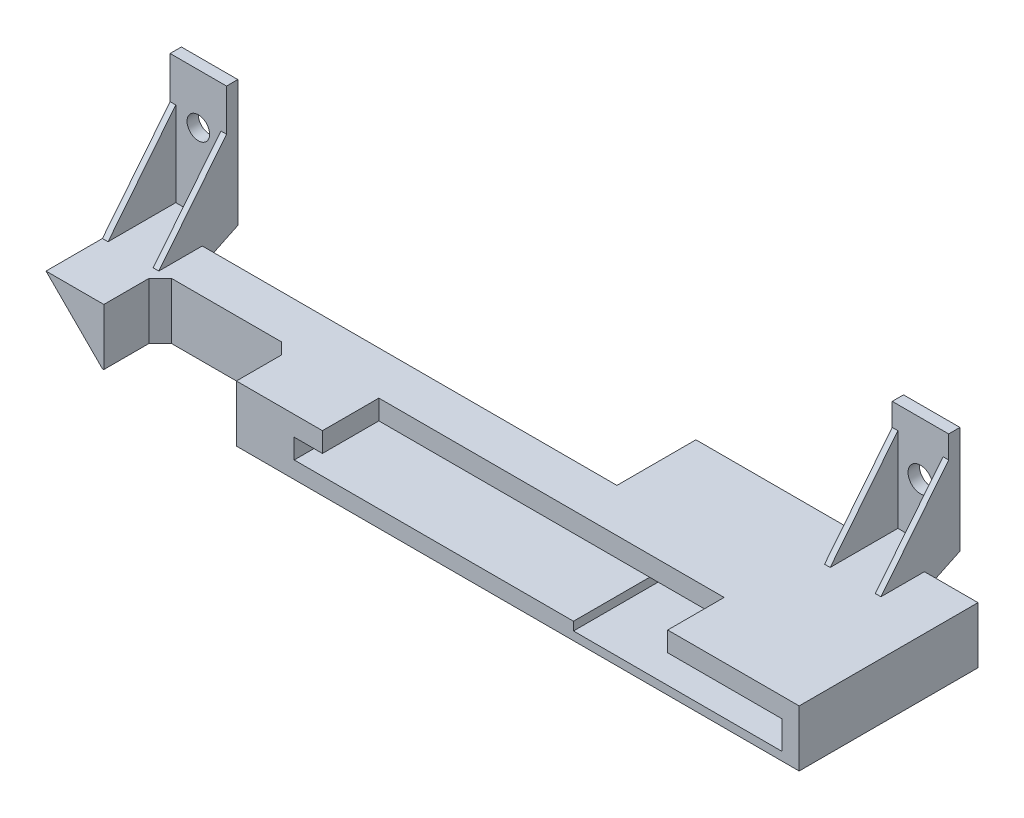
SolidWorks part; units mm, degrees
ref_plane "Front Plane" through (0, 0, 0) normal (1, 0, 0) x (0, 1, 0)
ref_plane "Top Plane" through (0, 0, 0) normal (0, 0, 1) x (0, 1, 0)
ref_plane "Right Plane" through (0, 0, 0) normal (0, 1, 0) x (-1, 0, 0)
sketch "Sketch1" plane through (0, 0, 0) normal (0, 0, 1) x (0, 1, 0)
  line L1 (-5, 25) -> (5, 25)
  line L2 (-5, 25) -> (-5, -25)
  line L3 (-5, -25) -> (5, -25)
  line L4 (5, 25) -> (5, -25)
  line L5 (-5, 25) -> (5, -25) construction
  line L6 (-5, -25) -> (5, 25) construction
  line L7 (-2.5, 12) -> (1.5, 12)
  line L8 (-2.5, 12) -> (-2.5, -18)
  line L9 (-2.5, -18) -> (1.5, -18)
  line L10 (1.5, 12) -> (1.5, -18)
  line L11 (-2.5, 12) -> (1.5, -18) construction
  line L12 (-2.5, -18) -> (1.5, 12) construction
  point P0 (0, 0)
  point P6 (-0.5, -3)
  point P11 (-1.611, -32.2076)
  point P12 (-1.6312, -32.9195)
  dimension "D1" = 10
  dimension "D2" = 50
  dimension "D3" = 4
  dimension "D4" = 30
  dimension "D5" = 2.5
  dimension "D6" = 7
extrude "Boss-Extrude1" add sketch "Sketch1" along normal blind 2
sketch "Sketch2" plane through (0, 0, 2) normal (0, 0, 1) x (1, 0, 0)
  line L0 (-25, 5) -> (-25, -5)
  line L1 (-25, 5) -> (-25, -5) construction
  line L2 (-25, -5) -> (25, -5) construction
  line L3 (-25, -5) -> (25, -5)
  line L4 (25, -5) -> (25, 5)
  line L5 (25, 5) -> (-25, 5)
  line L6 (22, 1.5) -> (22, -3.5)
  line L7 (22, -3.5) -> (-15, -3.5)
  line L8 (-15, -3.5) -> (-15, 1.5)
  line L9 (-15, 1.5) -> (22, 1.5)
  line L10 (18, 1.5) -> (-12, 1.5) construction
  dimension "D1" = 37
  dimension "D2" = 3
  dimension "D3" = 5
  dimension "D4" = 0
extrude "Boss-Extrude2" add sketch "Sketch2" along normal blind 12
sketch "Sketch6" plane through (0, 0, 14) normal (0, 0, 1) x (1, 0, 0)
  line L1 (25, -5) -> (-108.5, -5)
  line L2 (25, -5) -> (25, 5)
  line L3 (25, 5) -> (-108.5, 5)
  line L4 (-108.5, -5) -> (-108.5, 5)
  line L5 (-15, 1.5) -> (22, 1.5)
  line L6 (-15, 1.5) -> (-15, -3.5)
  line L7 (-15, -3.5) -> (22, -3.5)
  line L8 (22, 1.5) -> (22, -3.5)
  dimension "D1" = 133.5
extrude "Boss-Extrude7" add sketch "Sketch6" along normal blind 2
sketch "Sketch3" plane through (0, 0, 16) normal (0, 0, 1) x (1, 0, 0)
  line L0 (22, -3.5) -> (-15, -3.5)
  line L1 (-108.5, 5) -> (25, 5)
  line L2 (-108.5, 5) -> (-108.5, -5)
  line L3 (-108.5, -5) -> (25, -5)
  line L4 (25, 5) -> (25, -5)
  line L5 (22, 1.5) -> (-64.5, 1.5)
  line L6 (22, 1.5) -> (22, -3.5)
  line L8 (-64.5, 1.5) -> (-64.5, -2)
  line L9 (-15, -3.5) -> (-15, -2)
  line L11 (-15, -2) -> (-64.5, -2)
  line L12 (-15, -3.5) -> (22, -3.5) construction
  line L13 (-15, -3.5) -> (22, -3.5) construction
  point P11 (0, 0)
  point P16 (0, 0)
  point P17 (-99, 5)
  point P18 (0, 0)
  point P19 (0, 0)
  point P20 (25, -5)
  point P22 (0, 0)
  point P23 (0, 0)
  point P24 (0, 0)
  point P26 (-14, -3)
  point P28 (22, -3)
  point P33 (22, 1)
  dimension "D1" = 86.5
  dimension "D2" = 3.5
extrude "Boss-Extrude3" add sketch "Sketch3" along normal blind 5.7
sketch "Sketch4" plane through (0, 0, 21.7) normal (0, 0, 1) x (1, 0, 0)
  line L0 (-64.5, 1.5) -> (-59.5, 1.5)
  line L1 (-108.5, 5) -> (25, 5)
  line L2 (-108.5, 5) -> (-108.5, -5)
  line L3 (-108.5, -5) -> (25, -5)
  line L4 (25, 5) -> (25, -5)
  line L5 (22, 1.5) -> (-64.5, 1.5) construction
  line L6 (-59.5, 1.5) -> (-59.5, 5)
  line L7 (-59.5, 5) -> (1.7, 5)
  line L8 (1.7, 5) -> (1.7, 1.5)
  line L9 (1.7, 1.5) -> (22, 1.5)
  line L10 (22, 1.5) -> (22, -3.5)
  line L11 (22, -3.5) -> (-15, -3.5)
  line L12 (-15, -3.5) -> (-15, -2)
  line L13 (-15, -2) -> (-64.5, -2)
  line L14 (-64.5, -2) -> (-64.5, 1.5)
  line L15 (-98.25, 0) -> (-108.5, 0) construction
  line L16 (-98.25, 5) -> (-74.75, 5)
  line L17 (-98.25, 5) -> (-98.25, -5)
  line L18 (-98.25, -5) -> (-74.75, -5)
  line L19 (-74.75, 5) -> (-74.75, -5)
  line L20 (-74.75, 0) -> (-64.5, 0) construction
  line L21 (25, 5) -> (-108.5, 5) construction
  line M21 (-108.5, 5) -> (-108.5, -5)
  line M22 (-108.5, -5) -> (25, -5)
  line M23 (25, -5) -> (25, 5)
  line M24 (25, 5) -> (-108.5, 5)
  line M25 (-64.5, 1.5) -> (22, 1.5)
  line M26 (22, 1.5) -> (22, -3.5)
  line M27 (22, -3.5) -> (-15, -3.5)
  line M28 (-15, -3.5) -> (-15, -2)
  line M29 (-15, -2) -> (-64.5, -2)
  line M30 (-64.5, -2) -> (-64.5, 1.5)
  dimension "D1" = 61.2
  dimension "D2" = 5
  dimension "D3" = 23.5
extrude "Boss-Extrude4" add sketch "Sketch4" along normal blind 10 contours L17 L1 M21 M22 | L1 L19 L8 L6 M22 M23 M24 M25 M26 M27 M28 M29 M30 region at (-65.5025, -0.25, 21.7) region at (-103.375, 0, 21.7)
chamfer "Chamfer1" distance 2 angle 45 2 edges at (-98.25, 0, 21.7) (-74.75, 0, 21.7)
sketch "Sketch5" plane through (0, 0, 31.7) normal (0, 0, 1) x (1, 0, 0)
  line L0 (-108.5, 18.5) -> (-98.5, 18.5) construction
  line L1 (15.5, 5) -> (5.5, 5)
  line L2 (15.5, 5) -> (15.5, 24)
  line L3 (15.5, 24) -> (5.5, 24)
  line L4 (5.5, 5) -> (5.5, 24)
  line L5 (-108.5, 5) -> (-98.5, 5)
  line L6 (-108.5, 5) -> (-108.5, 27.4)
  line L7 (-108.5, 27.4) -> (-98.5, 27.4)
  line L8 (-98.5, 5) -> (-98.5, 27.4)
  line L9 (5.5, 14.5) -> (15.5, 14.5) construction
  line L11 (25, -5) -> (25, 5) construction
  line L13 (-98.25, 5) -> (-108.5, 5) construction
  line L15 (-108.5, 5) -> (-108.5, -5) construction
  line L16 (25, 5) -> (1.7, 5) construction
  circle A0 centre (10.5, 14.5) radius 2.2
  circle A1 centre (-103.5, 18.5) radius 2
  point P19 (0, 0)
  point P21 (0, 0)
  point P22 (0, 0)
  point P23 (0, 0)
  point P24 (0, 0)
  point P25 (0, 0)
  point P26 (0, 0)
  point P27 (0, 0)
  point P28 (0, 0)
  point P31 (0, 0)
  point P32 (-99, 5)
  point P34 (0, 0)
  point P37 (0, 0)
  point P38 (-107.9174, 5.7559)
  point P41 (-106.7869, 5)
  point P42 (0, 0)
  point P45 (15.5, 5)
  line M19 (25, 5) -> (1.7, 5)
  dimension "D2" = 4.4
  dimension "D3" = 4
  dimension "D4" = 4
  dimension "D5" = 19
  dimension "D6" = 22.4
  dimension "D7" = 10
  dimension "D8" = 10
  dimension "D9" = 9.5
  dimension "D10" = 124
  dimension "D11" = 9.5
extrude "Boss-Extrude5" add sketch "Sketch5" along normal blind 2 from offset 38 separate body contours L4 L2 L3 A0 M19 region at (10.5, 5.2147, 31.7) offset against normal yes
extrude "Boss-Extrude6" add sketch "Sketch5<3>" along normal blind 2 from offset 24 contours L5 L8 L7 L6 A1 region at (-103.5, 16.0633, 31.7) offset against normal yes
sketch "Sketch5<3>" plane through (0, 0, 31.7) normal (0, 0, 1) x (1, 0, 0) same geometry as "Sketch5"
sketch "Sketch7" plane through (15.5, 0, 0) normal (1, 0, 0) x (0, 1, 0)
  line L0 (5, -4.3) -> (20, -4.3)
  line L1 (5, -4.3) -> (24, -4.3) construction
  line L2 (20, -4.3) -> (5, 7.7)
  line L3 (5, 31.7) -> (5, 0) construction
  line L4 (5, 7.7) -> (5, -4.3)
  dimension "D1" = 15
  dimension "D2" = 12
extrude "Boss-Extrude8" add sketch "Sketch7" against normal blind 1
extrude "Boss-Extrude9" add sketch "Sketch7<2>" along normal blind 1 from surface starting at face at (5.5, 14.5, -5.3)
sketch "Sketch7<2>" plane through (15.5, 0, 0) normal (1, 0, 0) x (0, 1, 0) same geometry as "Sketch7"
sketch "Sketch8" plane through (-98.5, 0, 0) normal (1, 0, 0) x (0, 1, 0)
  line L0 (5, 9.7) -> (20, 9.7)
  line L1 (5, 9.7) -> (27.4, 9.7) construction
  line L2 (20, 9.7) -> (5, 21.7)
  line L3 (5, 31.7) -> (5, 0) construction
  line L4 (5, 21.7) -> (5, 9.7)
  dimension "D1" = 15
  dimension "D2" = 12
extrude "Boss-Extrude10" add sketch "Sketch8" against normal blind 1
extrude "Boss-Extrude11" add sketch "Sketch8<2>" along normal blind 1 from surface starting at face at (-108.5, 16.2, 8.7)
sketch "Sketch8<2>" plane through (-98.5, 0, 0) normal (1, 0, 0) x (0, 1, 0) same geometry as "Sketch8"
sketch "Sketch9" plane through (25, 0, 0) normal (1, 0, 0) x (0, 1, 0)
  line L0 (5, -6.3) -> (2, 0)
  line L1 (-5, 0) -> (5, 0) construction
  line L2 (2, 0) -> (5, 0)
  line L3 (5, 0) -> (5, -6.3)
  line L4 (5, 0) -> (5, -6.3) construction
  line L5 (-5, 0) -> (5, 0) construction
  point P5 (0, 0)
  point P8 (0, 0)
  point P9 (0, 0)
  point P10 (0, 0)
  point P11 (5, 0)
  point P16 (5, -6.3)
  dimension "D1" = 3
extrude "Boss-Extrude12" add sketch "Sketch9" against normal up to surface (19.5 mm away) from surface up to face at (5.5, 13.8333, -2.25) starting at face at (15.5, 13.8333, -2.25)
sketch "Sketch10" plane through (-98.5, 0, 0) normal (1, 0, 0) x (0, 1, 0)
  line L0 (5, 7.7) -> (5, 14)
  line L1 (5, 14) -> (2, 14)
  line L2 (2, 14) -> (5, 7.7)
  dimension "D1" = 3
extrude "Boss-Extrude13" add sketch "Sketch10" against normal up to surface (10 mm away) up to face at (-108.5, 9.4222, 16.4333)
chamfer "Chamfer2" distance 10 angle 45 1 edges at (-108.5, -5, 22.85)
